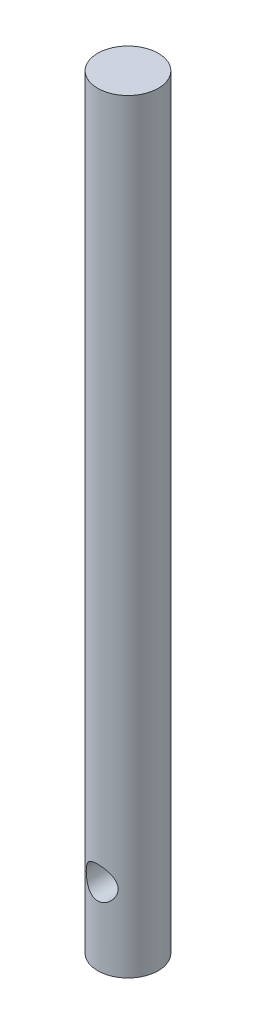
SolidWorks part; units mm, degrees
material "Plain Carbon Steel"
ref_plane "Front Plane" through (0, 0, 0) normal (0, 0, 1) x (1, 0, 0)
ref_plane "Top Plane" through (0, 0, 0) normal (0, 1, 0) x (1, 0, 0)
ref_plane "Right Plane" through (0, 0, 0) normal (1, 0, 0) x (0, 0, -1)
sketch "Sketch1" plane through (0, 0, 0) normal (0, 1, 0) x (1, 0, 0)
  circle A0 centre (0, 0) radius 4.7625
  dimension "D1" = 9.525
extrude "Boss-Extrude1" add sketch "Sketch1" along normal blind 120
sketch "Sketch2" plane through (0, 0, 0) normal (0, 0, 1) x (1, 0, 0)
  circle A0 centre (0, 12) radius 2.5
  dimension "D1" = 5
extrude "Cut-Extrude1" cut sketch "Sketch2" against normal mid plane 30
